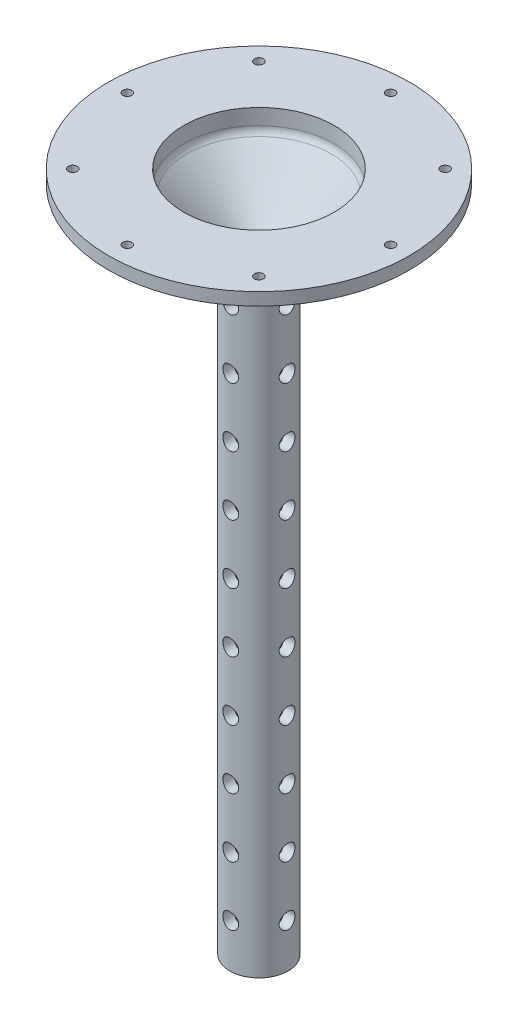
SolidWorks part; units mm, degrees
material "7075-T6 (SN)"
ref_plane "Front Plane" through (0, 0, 0) normal (0, 0, 1) x (1, 0, 0)
ref_plane "Top Plane" through (0, 0, 0) normal (0, 1, 0) x (1, 0, 0)
ref_plane "Right Plane" through (0, 0, 0) normal (1, 0, 0) x (0, 0, -1)
sketch "Sketch1" plane through (0, 0, 0) normal (0, 1, 0) x (1, 0, 0)
  circle A0 centre (0, 0) radius 38.1
  dimension "D1" = 76.2
extrude "Boss-Extrude1" add sketch "Sketch1" along normal blind 3.175
hole_wizard "Tap Drill for #4-40 Tap1" positions "Sketch3" profile "Sketch4" hole size "#4-40" standard "ANSI Inch" end condition through all
sketch "Sketch3" plane through (0, 0, 0) normal (0, -1, 0) x (-1, 0, 0)
  point P0 (0, -33.3375)
  dimension "D1" = 33.3375
sketch "Sketch4" plane through (0, 0, 33.3375) normal (1, 0, 0) x (0, 0, -1)
  line L0 (0, 0) -> (0, 3.175)
  line L1 (0, 3.175) -> (1.1303, 3.175)
  line L2 (1.1303, 3.175) -> (1.1303, 0)
  line L5 (1.1303, 0) -> (0, 0)
  line L11 (0, -6.35) -> (0, 107.95) construction
  dimension "Thru Hole Dia." = 2.2606
  dimension "Thru Hole Depth" = 3.175
pattern_circular "CirPattern1" count 8 over 360 about axis through (0, 0, 0) along (0, 1, 0) of "Tap Drill for #4-40 Tap1"
sketch "Sketch5" plane through (0, 0, 0) normal (0, -1, 0) x (1, 0, 0)
  circle A0 centre (0, 0) radius 25.4
  dimension "D1" = 50.8
extrude "Boss-Extrude2" add sketch "Sketch5" along normal blind 19.05
sketch "Sketch6" plane through (0, -19.05, 0) normal (0, -1, 0) x (1, 0, 0)
  circle A0 centre (0, 0) radius 4.7625
  dimension "D1" = 9.525
extrude "Cut-Extrude1" cut sketch "Sketch6" against normal through all both and the other way through all
sketch "Sketch7" plane through (0, 3.175, 0) normal (0, 1, 0) x (1, 0, 0)
  circle A0 centre (0, 0) radius 19.05
  dimension "D1" = 38.1
extrude "Cut-Extrude2" cut sketch "Sketch7" against normal blind 5.08
sketch "Sketch8" plane through (0, -1.905, 0) normal (0, 1, 0) x (1, 0, 0)
  circle A0 centre (0, 0) radius 19.05
  circle A1 centre (0, 0) radius 19.05 construction
  dimension "D1" = 0
ref_plane "Plane1" through (0, -15.875, 0) normal (0, -1, 0) x (-1, 0, 0)
sketch "Sketch9" plane through (0, -15.875, 0) normal (0, -1, 0) x (-1, 0, 0)
  circle A0 centre (0, 0) radius 4.7625
  circle A1 centre (0, 0) radius 4.7625 construction
  dimension "D1" = 0
loft "Cut-Loft1" cut profiles "Sketch8", "Sketch9" connector at (0, -1.905, 19.05) connector at (-1.301, -15.875, 4.5814)
chamfer "Chamfer1" distance 16.51 angle 45 1 edges at (0, -19.05, -25.4)
fillet "Fillet1" radius 2.54 1 edges at (0, 0, 25.4)
fillet "Fillet2" radius 2.54 1 edges at (0, -1.905, 19.05)
sketch "Sketch10" plane through (0, -19.05, 0) normal (0, -1, 0) x (1, 0, 0)
  circle A0 centre (0, 0) radius 4.7625
  circle A1 centre (0, 0) radius 7.39
  circle A2 centre (0, 0) radius 4.7625 construction
  circle A3 centre (0, 0) radius 8.89 construction
  dimension "D1" = 0
  dimension "D2" = 1.5
extrude "Boss-Extrude3" add sketch "Sketch10" along normal blind 150
sketch "Sketch11" plane through (0, 0, 0) normal (0, 0, 1) x (1, 0, 0)
  circle A0 centre (0, -23) radius 2
  dimension "D2" = 4
  dimension "D1" = 23
extrude "Cut-Extrude3" cut sketch "Sketch11" against normal through all both and the other way through all
pattern_circular "CirPattern2" count 4 over 360 about axis through (0, -169.05, 0) along (0, 1, 0) of "Cut-Extrude3" reverse direction yes
pattern_linear "LPattern1" count 10 spacing 15 along (0, -1, 0) of "Cut-Extrude3", "CirPattern2"
